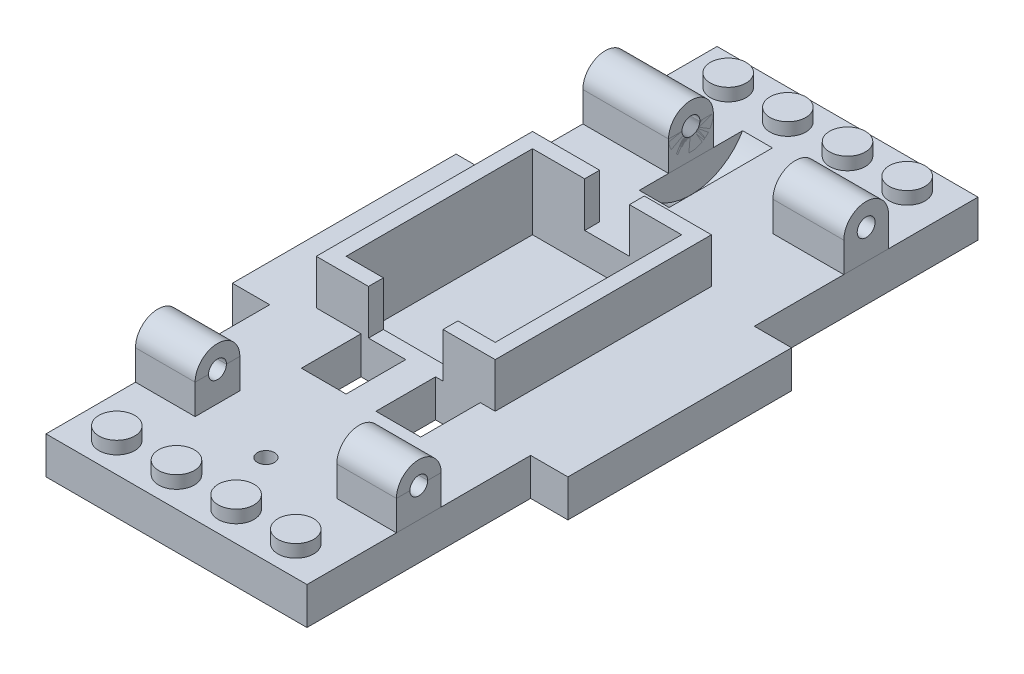
SolidWorks part; units mm, degrees
ref_plane "Front Plane" through (0, 0, 0) normal (0, 0, 1) x (1, 0, 0)
ref_plane "Top Plane" through (0, 0, 0) normal (0, 1, 0) x (1, 0, 0)
ref_plane "Right Plane" through (0, 0, 0) normal (1, 0, 0) x (0, 0, -1)
sketch "Sketch1" plane through (0, 0, 0) normal (0, 1, 0) x (1, 0, 0)
  line L0 (-17.5, -30) -> (17.5, -30) construction
  line L1 (-17.5, 45) -> (17.5, 45)
  line L2 (-17.5, 45) -> (-17.5, -45)
  line L3 (-17.5, -45) -> (17.5, -45)
  line L4 (17.5, 45) -> (17.5, -45)
  line L5 (-17.5, 45) -> (17.5, -45) construction
  line L6 (-17.5, -45) -> (17.5, 45) construction
  line L7 (-17.5, -33) -> (17.5, -33)
  line L8 (-17.5, -33) -> (-17.5, -27)
  line L10 (17.5, -33) -> (17.5, -27)
  line L11 (-17.5, 30) -> (17.5, 30) construction
  line L13 (-17.5, 33) -> (-17.5, 27)
  line L14 (-17.5, 27) -> (17.5, 27)
  line L15 (17.5, 33) -> (17.5, 27)
  line L16 (-17.5, -30) -> (17.5, -30)
  line L17 (-17.5, 30) -> (17.5, 30)
  line L18 (-17.5, -31.2) -> (17.5, -31.2)
  line L19 (0, 45) -> (0, -45) construction
  line L20 (-17.5, 30) -> (-6, 30)
  line L21 (-17.5, 30) -> (-17.5, 27)
  line L22 (-17.5, 27) -> (-6, 27)
  line L23 (-6, 30) -> (-6, 27)
  line L24 (17.5, 27) -> (8, 27)
  line L25 (17.5, 27) -> (17.5, 30)
  line L26 (17.5, 30) -> (8, 30)
  line L27 (8, 27) -> (8, 30)
  line L28 (-6, 28.8) -> (8, 28.8)
  line L29 (-17.5, 30) -> (-6, 30)
  line L30 (-17.5, 30) -> (-17.5, 28.8)
  line L31 (-17.5, 28.8) -> (-6, 28.8)
  line L32 (-6, 30) -> (-6, 28.8)
  line L33 (8, 30) -> (17.5, 30)
  line L34 (8, 30) -> (8, 28.8)
  line L35 (8, 28.8) -> (17.5, 28.8)
  line L36 (17.5, 30) -> (17.5, 28.8)
  line L37 (-17.5, -30) -> (-9.5, -30)
  line L38 (-17.5, -30) -> (-17.5, -33)
  line L39 (-17.5, -33) -> (-9.5, -33)
  line L40 (-9.5, -30) -> (-9.5, -33)
  line L41 (-17.5, -31.2) -> (-9.5, -31.2)
  line L42 (-17.5, -31.2) -> (-17.5, -33)
  line L43 (-17.5, -33) -> (-9.5, -33)
  line L44 (-9.5, -31.2) -> (-9.5, -33)
  line L45 (17.5, -33) -> (9.5, -33)
  line L46 (17.5, -33) -> (17.5, -30)
  line L47 (17.5, -30) -> (9.5, -30)
  line L48 (9.5, -33) -> (9.5, -30)
  line L49 (17.5, -33) -> (9.5, -33)
  line L50 (17.5, -33) -> (17.5, -31.2)
  line L51 (17.5, -31.2) -> (9.5, -31.2)
  line L52 (9.5, -33) -> (9.5, -31.2)
  line L53 (-17.5, 33) -> (17.5, 33)
  line L54 (-17.5, -27) -> (17.5, -27)
  line L55 (-9.5, -33) -> (-9.5, -27)
  line L56 (9.5, -33) -> (9.5, -27)
  line L57 (8, 27) -> (8, 33)
  line L58 (-6, 27) -> (-6, 33)
  line L59 (-17.5, 0) -> (17.5, 0) construction
  line L60 (-9.5, -27) -> (-17.5, -27)
  line L61 (-9.5, -27) -> (-9.5, -33)
  line L62 (-9.5, -33) -> (-17.5, -33)
  line L63 (-17.5, -27) -> (-17.5, -33)
  line L64 (17.5, -27) -> (9.5, -27)
  line L65 (17.5, -27) -> (17.5, -33)
  line L66 (17.5, -33) -> (9.5, -33)
  line L67 (9.5, -27) -> (9.5, -33)
  line L72 (-6, 30) -> (-2, 30)
  line L73 (-6, 30) -> (-6, 38)
  line L74 (-6, 38) -> (-2, 38)
  line L75 (-2, 30) -> (-2, 38)
  line L76 (-2, 30) -> (8, 30)
  line L77 (-2, 30) -> (-2, 34)
  line L78 (-2, 34) -> (8, 34)
  line L79 (8, 30) -> (8, 34)
  line L80 (-17.5, -15) -> (-22.5, -15)
  line L81 (17.5, 15) -> (22.5, 15)
  line L82 (17.5, 15) -> (17.5, -15)
  line L83 (17.5, -15) -> (22.5, -15)
  line L84 (22.5, 15) -> (22.5, -15)
  line L85 (-22.5, 15) -> (-22.5, -15)
  line L86 (-17.5, 15) -> (-22.5, 15)
  line L87 (-17.5, 15) -> (-17.5, -15)
  circle A0 centre (-4, -41) radius 2.4
  circle A1 centre (4, -41) radius 2.4
  circle A2 centre (12, -41) radius 2.4
  circle A3 centre (-12, -41) radius 2.4
  circle A7 centre (12, 41) radius 2.4
  circle A8 centre (4, 41) radius 2.4
  circle A9 centre (-4, 41) radius 2.4
  circle A10 centre (-12, 41) radius 2.4
  point P0 (0, 0)
  point P26 (0, 30)
  point P68 (22.5, 0)
  dimension "D19" = 4.8
  dimension "D1" = 90
  dimension "D2" = 35
  dimension "D3" = 6
  dimension "D4" = 12
  dimension "D5" = 3
  dimension "D6" = 12
  dimension "D7" = 6
  dimension "D8" = 3
  dimension "D9" = 1.2
  dimension "D10" = 6
  dimension "D11" = 8
  dimension "D12" = 1.2
  dimension "D13" = 1.2
  dimension "D14" = 8
  dimension "D15" = 8
  dimension "D16" = 8
  dimension "D17" = 4
  dimension "D18" = 4
  dimension "D20" = 4
  dimension "D21" = 4
  dimension "D25" = 15
  dimension "D26" = 5
  dimension "D22" = 3
  dimension "D23" = 2
  dimension "D24" = 1
extrude "Boss-Extrude1" add sketch "Sketch1" against normal blind 4 contours L35 L27 L14 L25 | L27 L35 L15 L17 | L57 L17 L4 L53 | L31 L21 L14 L23 | L13 L31 L23 L17 | L17 L58 L53 L2 | L65 L64 L67 L66 | L61 L60 L63 L62 region at (-11.75, 0, -31.5) region at (12.75, 0, -31.5) region at (-11.75, 0, -29.4) region at (12.75, 0, -29.4) region at (-11.75, 0, -27.9) region at (12.75, 0, -27.9)
revolve "Revolve1" add sketch "Sketch1<3>" angle 180 about L16 region at (-13.5, 0, 32.1) region at (13.5, 0, 32.1) reverse direction yes
sketch "Sketch1<3>" plane through (0, 0, 0) normal (0, 1, 0) x (1, 0, 0) same geometry as "Sketch1"
revolve "Revolve2" add sketch "Sketch1<5>" angle 360 about L17 region at (-11.75, 0, -27.9) region at (12.75, 0, -27.9)
sketch "Sketch1<5>" plane through (0, 0, 0) normal (0, 1, 0) x (1, 0, 0) same geometry as "Sketch1"
revolve "Cut-Revolve2" cut sketch "Sketch1<6>" angle 360 about L17 region at (-11.75, 0, -29.4) region at (12.75, 0, -29.4) region at (1, 0, -29.4)
sketch "Sketch1<6>" plane through (0, 0, 0) normal (0, 1, 0) x (1, 0, 0) same geometry as "Sketch1"
extrude "Boss-Extrude2" add sketch "Sketch1<7>" against normal blind 5 from offset 4 separate body contours L3 L4 L1 L2 | L80 L85 L86 L87 | L82 L81 L84 L83 offset against normal yes
sketch "Sketch1<7>" plane through (0, 0, 0) normal (0, 1, 0) x (1, 0, 0) same geometry as "Sketch1"
revolve "Cut-Revolve7" cut sketch "Sketch1<9>" angle 360 about L16 region at (-13.5, 0, 30.6) region at (13.5, 0, 30.6)
sketch "Sketch1<9>" plane through (0, 0, 0) normal (0, 1, 0) x (1, 0, 0) same geometry as "Sketch1"
revolve "Cut-Revolve8" cut sketch "Sketch1<10>" angle 360 about L17 region at (-4, 0, -35.5) region at (-4, 0, -31.5) region at (3, 0, -31.5) region at (3, 0, -33.5)
sketch "Sketch1<10>" plane through (0, 0, 0) normal (0, 1, 0) x (1, 0, 0) same geometry as "Sketch1"
sketch "Sketch4" plane through (0, -4, 0) normal (0, 1, 0) x (1, 0, 0)
  line L0 (-2, -10.25) -> (-2, 39.8847) construction
  line L1 (-12, 14.75) -> (-5, 14.75)
  line L2 (-12, 14.75) -> (-12, -10.25)
  line L3 (-12, -10.25) -> (8, -10.25)
  line L4 (8, 14.75) -> (8, -10.25)
  line L5 (-6, 23.0718) -> (-6, 36.9282) construction
  line L6 (1, 16.75) -> (10, 16.75)
  line L7 (-14, -12.25) -> (10, -12.25)
  line L8 (-14, -12.25) -> (-14, 16.75)
  line L9 (-14, 16.75) -> (-5, 16.75)
  line L10 (10, -12.25) -> (10, 16.75)
  line L11 (-14, -12.25) -> (10, 16.75) construction
  line L12 (-14, 16.75) -> (10, -12.25) construction
  line L14 (-5, 16.75) -> (-5, 14.75)
  line L16 (1, 16.75) -> (1, 14.75)
  line L17 (-5, 14.75) -> (8, 14.75)
  line L18 (3, -10.25) -> (3, -12.25)
  line L19 (-7, -10.25) -> (-7, -12.25)
  point P8 (-2, 2.25)
  point P13 (-6, 30)
  dimension "D1" = 25
  dimension "D2" = 20
  dimension "D3" = 4
  dimension "D4" = 2
  dimension "D5" = 2
  dimension "D6" = 15.25
  dimension "D7" = 2
  dimension "D8" = 7
  dimension "D9" = 7
  dimension "D10" = 5
  dimension "D11" = 5
  dimension "D12" = 12.5
extrude "Cut-Extrude2" cut sketch "Sketch4" against normal blind 4 contours L17 L4 L3 L2 L1
sketch "Sketch9" plane through (0, -9, 0) normal (0, -1, 0) x (1, 0, 0)
  line L0 (0, 45) -> (0, -45) construction
  line L1 (-17.5, 45) -> (17.5, 45) construction
  line L2 (-17.5, -45) -> (17.5, -45) construction
  circle A0 centre (0, 33) radius 1.15
  circle A1 centre (0, -20) radius 1.15
  point P9 (0, 0)
  dimension "D4" = 20
  dimension "D2" = 2.3
  dimension "D3" = 2.3
  dimension "D1" = 12
extrude "Cut-Extrude4" cut sketch "Sketch9" against normal up to next (5 mm away)
sketch "Sketch10" plane through (0, -4, 0) normal (0, 1, 0) x (1, 0, 0)
  line L0 (-14, -12.25) -> (10, -12.25) construction
  line L1 (-8, -12.25) -> (-2, -12.25)
  line L2 (-8, -12.25) -> (-8, -20.25)
  line L3 (-8, -20.25) -> (-2, -20.25)
  line L4 (-2, -12.25) -> (-2, -20.25)
  line L6 (2, -12.25) -> (8, -12.25)
  line L7 (2, -12.25) -> (2, -20.25)
  line L8 (2, -20.25) -> (8, -20.25)
  line L9 (8, -12.25) -> (8, -20.25)
  circle A0 centre (0, -33) radius 1.15 construction
  point P12 (5, -20.25)
  dimension "D1" = 4
  dimension "D2" = 2
  dimension "D3" = 6
  dimension "D4" = 8
  dimension "D5" = 8
  dimension "D6" = 6
extrude "Cut-Extrude5" cut sketch "Sketch10" against normal up to next (5 mm away) contours L2 L1 L4 L3 | L7 L6 L9 L8
extrude "Boss-Extrude3" add sketch "Sketch4<6>" along normal blind 6 contours L19 L3 L2 L1 L14 L9 L8 L7 | L3 L18 L7 L10 L6 L16 L17 L4 region at (-12.3036, -4, -2.25) region at (1.3036, -4, -15.75)
sketch "Sketch4<6>" plane through (0, -4, 0) normal (0, 1, 0) x (1, 0, 0) same geometry as "Sketch4"
extrude "Boss-Extrude4" add sketch "Sketch1<12>" against normal blind 1.7 from offset 2.3 separate body contours A9 | A8 | A10 | A7 | A2 | A1 | A0 | A3 | A10 region at (-4, 0, 41) region at (4, 0, 41) region at (12, 0, 41) region at (-12, 0, 41) region at (12, 0, -41) region at (4, 0, -41) region at (-4, 0, -41) region at (-12, 0, -41) offset against normal yes
sketch "Sketch1<12>" plane through (0, 0, 0) normal (0, 1, 0) x (1, 0, 0) same geometry as "Sketch1"
